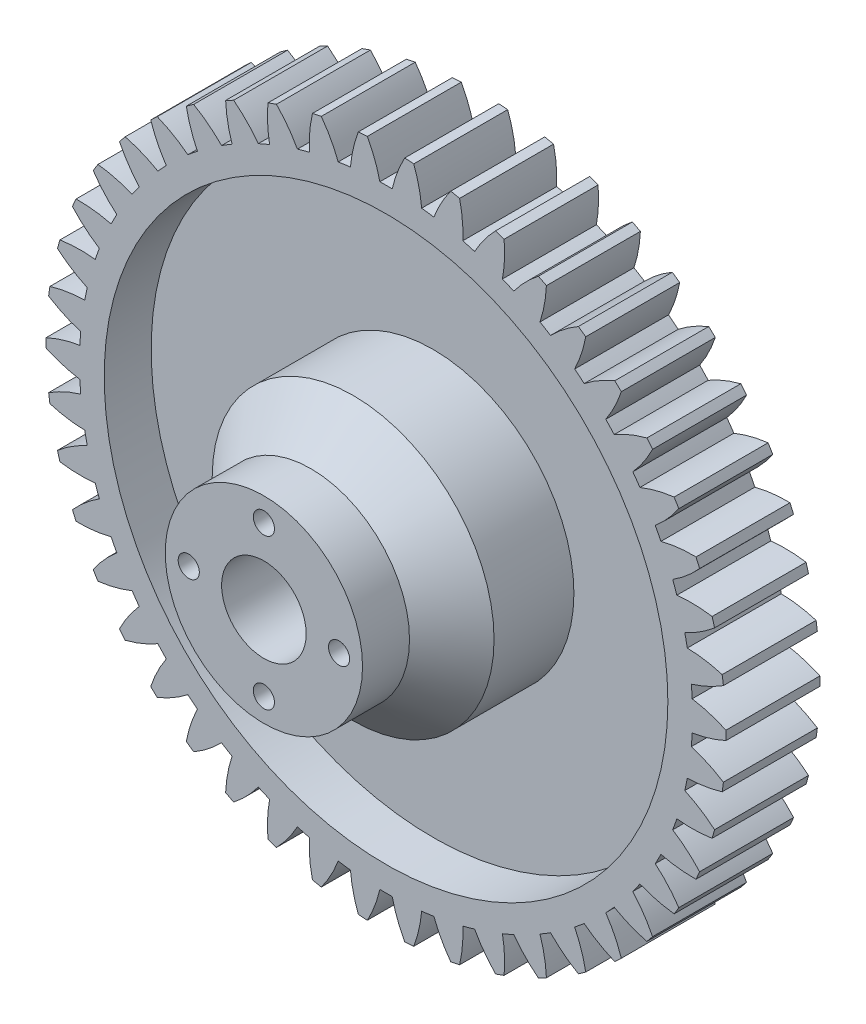
SolidWorks part; units mm, degrees
ref_plane "Plan de face" through (0, 0, 0) normal (0, 0, 1) x (1, 0, 0)
ref_plane "Plan de dessus" through (0, 0, 0) normal (0, 1, 0) x (1, 0, 0)
ref_plane "Plan de droite" through (0, 0, 0) normal (1, 0, 0) x (0, 0, -1)
sketch "Esquisse1" plane through (0, 0, 0) normal (0, 0, 1) x (1, 0, 0)
  line L0 (0, 8) -> (0, 0) construction
  circle A0 centre (0, 0) radius 36.1859
  point P15 (0, 0)
  dimension "D1" = 72.3719
extrude "Boss.-Extru.1" add sketch "Esquisse1" along normal blind 10
sketch "Esquisse2" plane through (0, 0, 10) normal (0, 0, 1) x (1, 0, 0)
  line L0 (0, 32.624) -> (0, 0) construction
  line L1 (0, 0) -> (-0.6558, 32.6174) construction
  line L2 (0, 0) -> (0.6558, 32.6174) construction
  line L5 (0, 0) -> (-1.9895, 36.1312) construction
  line L6 (1.9895, 36.1312) -> (0, 0) construction
  arc A0 (-0.6558, 32.6174) -> (0.6558, 32.6174) centre (0, 0) cw
  circle A3 centre (0, 0) radius 36.1859 construction
  arc A4 (-1.9895, 36.1312) -> (1.9895, 36.1312) centre (0, 0) cw
  arc A7 (-1.9895, 36.1312) -> (-0.6558, 32.6174) centre (-14.1043, 29.5228) cw
  arc A8 (0.6558, 32.6174) -> (1.9895, 36.1312) centre (14.1043, 29.5228) cw
  point P13 (0, 36.1859)
  dimension "D1" = 32.624
  dimension "D5" = 13.8
  dimension "D6" = 13.8
  dimension "D2" = 2.304
  dimension "D4" = 6.303
extrude "Enlèv. mat.-Extru.1" cut sketch "Esquisse2" against normal up to next
pattern_circular "Répétition circulaire1" count 46 over 360 about axis through (0, 0, 10) along (0, 0, 1) of "Enlèv. mat.-Extru.1"
sketch "Esquisse3" plane through (0, 0, 10) normal (0, 0, 1) x (1, 0, 0)
  circle A0 centre (0, 0) radius 4.5
  dimension "D1" = 9
extrude "Enlèv. mat.-Extru.2" cut sketch "Esquisse3" against normal up to next
sketch "Esquisse4" plane through (0, 0, 10) normal (0, 0, 1) x (1, 0, 0)
  circle A0 centre (0, 8) radius 1.125
  circle A1 centre (8, 0) radius 1.125
  circle A2 centre (0, -8) radius 1.125
  circle A3 centre (-8, 0) radius 1.125
  point P12 (0, 0)
  dimension "D1" = 2.25
  dimension "D2" = 8
extrude "Enlèv. mat.-Extru.3" cut sketch "Esquisse4" against normal up to next
sketch "Esquisse5" plane through (0, 0, 10) normal (0, 0, 1) x (1, 0, 0)
  circle A0 centre (0, 0) radius 15
  circle A1 centre (0, -8) radius 1.125 construction
  circle A2 centre (-8, 0) radius 1.125 construction
  circle A3 centre (0, 8) radius 1.125 construction
  circle A4 centre (8, 0) radius 1.125 construction
  circle A5 centre (0, 0) radius 4.5 construction
  circle A6 centre (0, -8) radius 1.125
  circle A7 centre (-8, 0) radius 1.125
  circle A8 centre (0, 8) radius 1.125
  circle A9 centre (8, 0) radius 1.125
  circle A10 centre (0, 0) radius 4.5
  dimension "D1" = 30
extrude "Boss.-Extru.2" add sketch "Esquisse5" along normal blind 13
sketch "Esquisse6" plane through (0, 0, 0) normal (0, 0, -1) x (-1, 0, 0)
  circle A0 centre (0, 8) radius 2.5
  circle A1 centre (8, 0) radius 2.5
  circle A2 centre (0, -8) radius 2.5
  circle A3 centre (-8, 0) radius 2.5
  dimension "D1" = 5
extrude "Enlèv. mat.-Extru.4" cut sketch "Esquisse6" against normal offset from surface (14 mm away) 9 up to face at (9.125, 0, 23)
sketch "Esquisse7" plane through (0, 0, 10) normal (0, 0, 1) x (1, 0, 0)
  circle A0 centre (0, 0) radius 30
  circle A1 centre (0, 0) radius 15 construction
  circle A2 centre (0, 0) radius 15
  dimension "D1" = 60
extrude "Enlèv. mat.-Extru.7" cut sketch "Esquisse7" against normal blind 5
sketch "Esquisse8" plane through (0, 0, 23) normal (0, 0, 1) x (1, 0, 0)
  circle A0 centre (0, 0) radius 10.5
  circle A1 centre (0, 0) radius 15 construction
  circle A2 centre (0, 0) radius 15
  dimension "D1" = 21
extrude "Enlèv. mat.-Extru.8" cut sketch "Esquisse8" against normal blind 5
chamfer "Chanfrein1" distance 4.5 angle 45 1 edges at (15, 0, 18)
